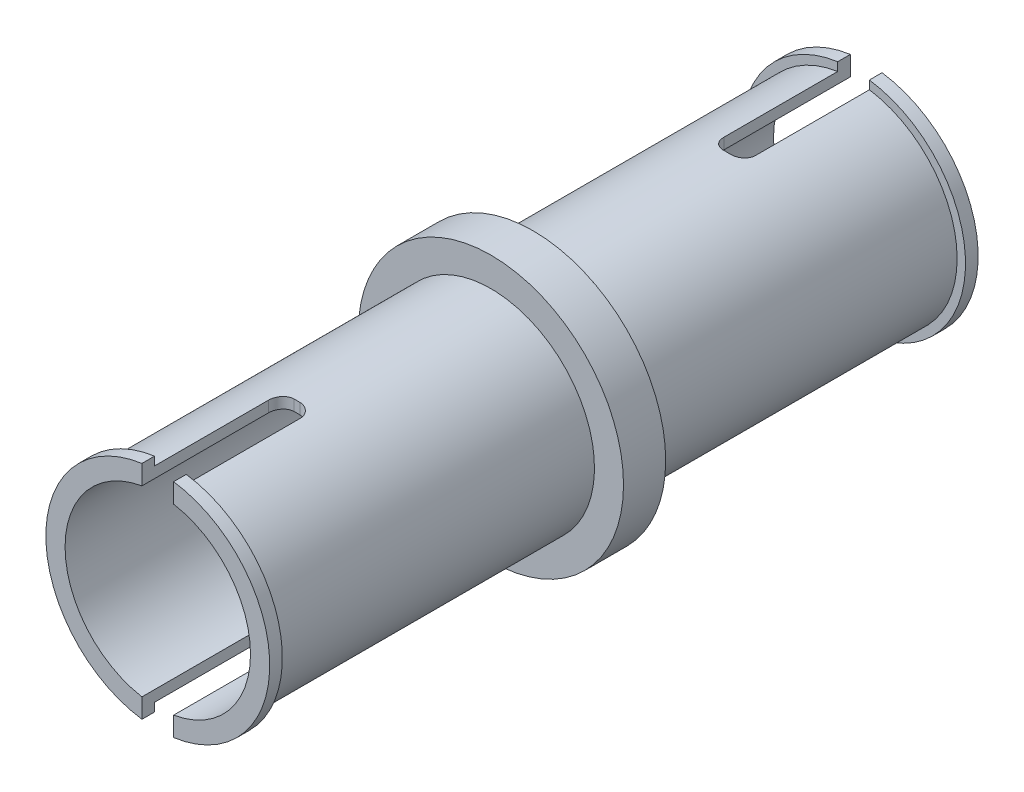
SolidWorks part; units mm, degrees
ref_plane "Front Plane" through (0, 0, 0) normal (0, 0, 1) x (1, 0, 0)
ref_plane "Top Plane" through (0, 0, 0) normal (0, 1, 0) x (1, 0, 0)
ref_plane "Right Plane" through (0, 0, 0) normal (1, 0, 0) x (0, 0, -1)
sketch "Sketch1" plane through (0, 0, 0) normal (0, 0, 1) x (1, 0, 0)
  line L0 (-2.4, 0) -> (2.4, 0)
  line L1 (-2.4, 0.895) -> (-2.4, -0.895)
  line L2 (-2.4, 0.895) -> (-0.9, 0.895)
  line L3 (0, 2.4) -> (0, -2.4)
  line L4 (-0.9, 0.895) -> (-0.9, 2.4)
  line L5 (-0.9, 2.4) -> (0.9, 2.4)
  line L6 (0.9, 0.895) -> (0.9, 2.4)
  line L7 (2.4, 0.895) -> (0.9, 0.895)
  line L8 (2.4, 0.895) -> (2.4, -0.895)
  line L9 (2.4, -0.895) -> (0.9, -0.895)
  line L10 (0.9, -0.895) -> (0.9, -2.4)
  line L11 (-0.9, -2.4) -> (0.9, -2.4)
  line L12 (-0.9, -0.895) -> (-0.9, -2.4)
  line L13 (-2.4, -0.895) -> (-0.9, -0.895)
  point P4 (0, 0)
  point P8 (-2.4, 0)
  point P12 (0, 0)
  dimension "D1" = 4.8
  dimension "D2" = 1.79
  dimension "D3" = 1.5
  dimension "D4" = 4.8
extrude "Boss-Extrude1" add sketch "Sketch1" along normal blind 7.9 contours L5 L4 L2 L1 L0 L3 | L1 L13 L12 L11 L3 L0 | L8 L7 L6 L5 L3 L0 | L3 L11 L10 L9 L8 L0 region at (-2.3661, 0.4475, 0) region at (-1.2, -0.0339, 0) region at (0.0339, 1.2, 0) region at (1.2, -0.0339, 0)
sketch "Sketch2" plane through (0, 0, 0) normal (0, 0, -1) x (-1, 0, 0)
  circle A0 centre (0, 0) radius 3.1445
extrude "Boss-Extrude3" add sketch "Sketch2" along normal blind 0.5 contours A0
sketch "Sketch3" plane through (0, 0, -0.5) normal (0, 0, -1) x (-1, 0, 0)
  circle A0 centre (0, 0) radius 2.4559
  dimension "D1" = 4.9118
extrude "Boss-Extrude4" add sketch "Sketch3" along normal blind 7.9
sketch "Sketch4" plane through (0, 0, -8.4) normal (0, 0, -1) x (-1, 0, 0)
  circle A0 centre (0, 0) radius 2.6546
extrude "Boss-Extrude5" add sketch "Sketch4" against normal blind 0.3
sketch "Sketch5" plane through (0, 0, -8.4) normal (0, 0, -1) x (-1, 0, 0)
  circle A0 centre (0, 0) radius 2.1986
extrude "Cut-Extrude1" cut sketch "Sketch5" against normal up to surface (7.9 mm away) up to face at (-2.4559, 0, -0.5)
sketch "Sketch6" plane through (0, 0, -8.4) normal (0, 0, -1) x (-1, 0, 0)
  line L0 (0, 0) -> (2.6546, 0) construction
  line L1 (0, 0) -> (0, 2.6546) construction
  line L2 (0.3755, 2.6546) -> (0.3755, 2.1663)
  line L3 (0.3755, 2.6546) -> (-0.3755, 2.6546)
  line L4 (0, 2.6546) -> (0, 2.1663)
  line L5 (0.3755, 2.1663) -> (-0.3755, 2.1663)
  line L6 (-0.3755, 2.6546) -> (-0.3755, 2.1663)
  line L7 (0.3755, -2.6546) -> (0.3755, -2.1663)
  line L8 (0.3755, -2.6546) -> (-0.3755, -2.6546)
  line L9 (-0.3755, -2.6546) -> (-0.3755, -2.1663)
  line L10 (0.3755, -2.1663) -> (-0.3755, -2.1663)
  circle A0 centre (0, 0) radius 2.6546 construction
  circle A1 centre (0, 0) radius 2.1986 construction
  circle M8 centre (0, 0) radius 2.1986
  circle M9 centre (0, 0) radius 2.6546
extrude "Cut-Extrude2" cut sketch "Sketch6" against normal blind 3.3 contours L4 L2 M9 M8 | L6 L4 M9 M8 | L9 L7 M9 M8 region at (-0.1881, 2.4168, -8.4) region at (0.1881, 2.4168, -8.4) region at (0, -2.4168, -8.4)
fillet "Fillet1" radius 0.3 4 edges at (-0.3755, -2.2967, -5.1) (0.3755, -2.2967, -5.1) (-0.3755, 2.2967, -5.1) (0.3755, 2.2967, -5.1)
sketch "Sketch7" plane through (0, 0, 0) normal (0, 0, 1) x (1, 0, 0)
  circle A0 centre (0, 0) radius 3.1445
extrude "Cut-Extrude5" cut sketch "Sketch7" along normal blind 9
mirror "Mirror3" of bodies 112
